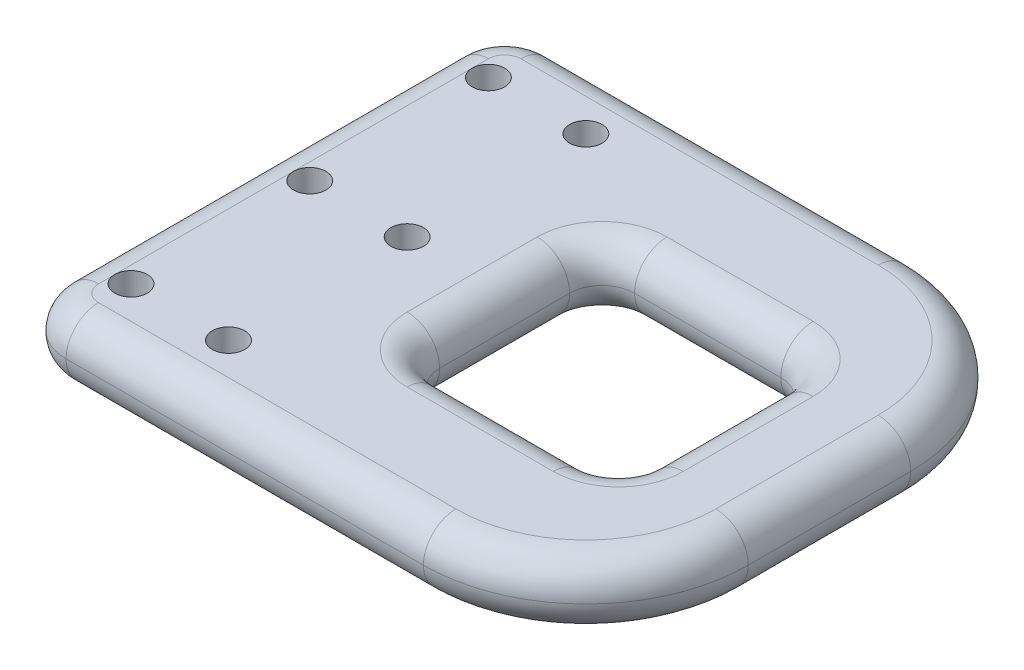
SolidWorks part; units mm, degrees
ref_plane "Front Plane" through (0, 0, 0) normal (0, 0, 1) x (1, 0, 0)
ref_plane "Top Plane" through (0, 0, 0) normal (0, 1, 0) x (1, 0, 0)
ref_plane "Right Plane" through (0, 0, 0) normal (1, 0, 0) x (0, 0, -1)
sketch "Sketch1" plane through (0, 0, 0) normal (0, 1, 0) x (1, 0, 0)
  line L1 (-14.5, 15) -> (7.5, 15)
  line L2 (-17.5, 12) -> (-17.5, -12)
  line L3 (-14.5, -15) -> (7.5, -15)
  line L4 (17.5, 5) -> (17.5, -5)
  line L5 (-17.5, 15) -> (17.5, -15) construction
  line L6 (-17.5, -15) -> (17.5, 15) construction
  line L7 (-0.5, 6) -> (8.5, 6)
  line L8 (-2.5, 4) -> (-2.5, -4)
  line L9 (-0.5, -6) -> (8.5, -6)
  line L10 (10.5, 4) -> (10.5, -4)
  line L11 (-2.5, 6) -> (10.5, -6) construction
  line L12 (-2.5, -6) -> (10.5, 6) construction
  line L13 (-14.5, 11) -> (-8.5, 11) construction
  line L14 (-14.5, 11) -> (-14.5, -11) construction
  line L15 (-14.5, -11) -> (-8.5, -11) construction
  line L16 (-8.5, 11) -> (-8.5, -11) construction
  line L17 (-14.5, 11) -> (-8.5, -11) construction
  line L18 (-14.5, -11) -> (-8.5, 11) construction
  circle A0 centre (-8.5, 11) radius 1
  circle A1 centre (-14.5, 11) radius 1
  circle A2 centre (-14.5, -11) radius 1
  circle A3 centre (-8.5, -11) radius 1
  circle A4 centre (-8.5, 0) radius 1
  circle A5 centre (-14.5, 0) radius 1
  arc A6 (7.5, -15) -> (17.5, -5) centre (7.5, -5) ccw
  arc A7 (17.5, 5) -> (7.5, 15) centre (7.5, 5) ccw
  arc A8 (-0.5, 6) -> (-2.5, 4) centre (-0.5, 4) ccw
  arc A9 (-2.5, -4) -> (-0.5, -6) centre (-0.5, -4) ccw
  arc A10 (8.5, -6) -> (10.5, -4) centre (8.5, -4) ccw
  arc A11 (10.5, 4) -> (8.5, 6) centre (8.5, 4) ccw
  arc A12 (-14.5, -15) -> (-17.5, -12) centre (-14.5, -12) cw
  arc A13 (-17.5, 12) -> (-14.5, 15) centre (-14.5, 12) cw
  point P0 (0, 0)
  point P6 (4, 0)
  point P12 (-11.5, 0)
  point P24 (-9.755, 0)
  point P43 (-4.3551, 9.4196)
  point P44 (-8.832, 0)
  point P45 (-0.5, -6)
  dimension "D6" = 4
  dimension "D7" = 2
  dimension "D8" = 3
  dimension "D9" = 10
  dimension "D10" = 2
  dimension "D13" = 3
  dimension "D2" = 30
  dimension "D3" = 12
  dimension "D4" = 13
  dimension "D5" = 7
  dimension "D11" = 6
  dimension "D12" = 35
extrude "Boss-Extrude1" add sketch "Sketch1" along normal mid plane 4
fillet "Fillet1" radius 2 32 edges at (14.5711, -2, 12.0711) (-3.5, -2, 15) (-16.6213, -2, 14.1213) (-17.5, -2, 0) (-16.6213, -2, -14.1213) (-3.5, -2, -15) (14.5711, -2, -12.0711) (14.5711, 2, 12.0711) (-3.5, 2, 15) (-16.6213, 2, 14.1213) (-17.5, 2, 0) (-16.6213, 2, -14.1213) (-3.5, 2, -15) (14.5711, 2, -12.0711) (9.9142, -2, 5.4142) (4, -2, 6) (-1.9142, -2, 5.4142) (-2.5, -2, 0) (-1.9142, -2, -5.4142) (4, -2, -6) (9.9142, -2, -5.4142) (-1.9142, 2, -5.4142) (4, 2, -6) (9.9142, 2, -5.4142) (10.5, 2, 0) (9.9142, 2, 5.4142) (4, 2, 6) (-1.9142, 2, 5.4142) (17.5, -2, 0) (17.5, 2, 0) (10.5, -2, 0) (-2.5, 2, 0)
equation "\"Tab_Thickness\"= 4"
equation "\"D1@Boss-Extrude1\"=\"Tab_Thickness\""
equation "\"D1@Fillet1\" = \"Tab_Thickness\" / 2"
